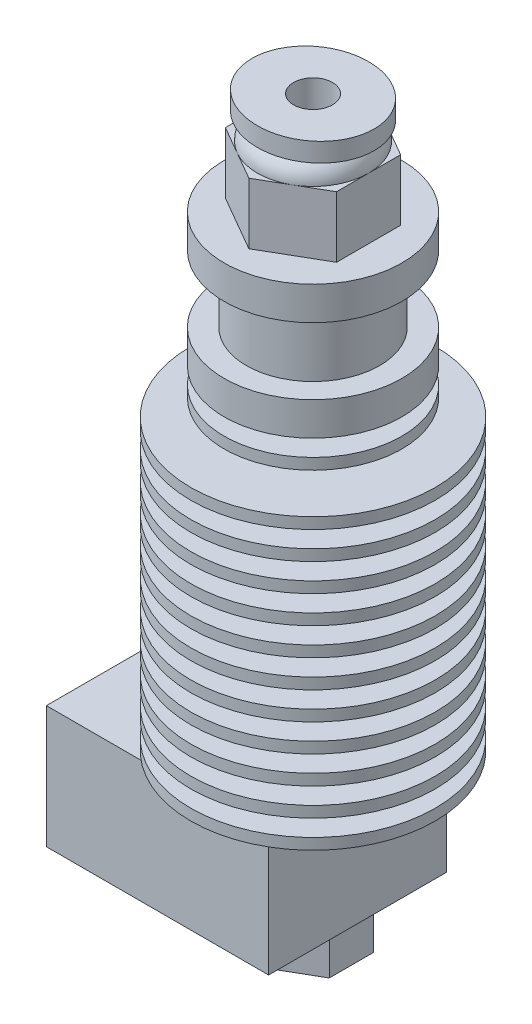
SolidWorks part; units mm, degrees
material "1023 Chapa de acero al carbono (SS)"
ref_plane "Alzado" through (0, 0, 0) normal (0, 0, 1) x (1, 0, 0)
ref_plane "Planta" through (0, 0, 0) normal (0, 1, 0) x (1, 0, 0)
ref_plane "Vista lateral" through (0, 0, 0) normal (1, 0, 0) x (0, 0, -1)
sketch "Croquis1" plane through (0, 0, 0) normal (0, 0, 1) x (1, 0, 0)
  line L0 (0, 0) -> (0, 42)
  line L1 (0, 42) -> (8, 42)
  line L2 (8, 42) -> (8, 39)
  line L3 (8, 39) -> (6, 39)
  line L4 (6, 39) -> (6, 33)
  line L5 (6, 33) -> (8, 33)
  line L6 (8, 33) -> (8, 30)
  line L7 (8, 30) -> (4.5, 30)
  line L8 (4.5, 30) -> (4.5, 28.5)
  line L9 (4.5, 28.5) -> (8, 28.5)
  line L10 (8, 28.5) -> (8, 27.5)
  line L11 (8, 27.5) -> (4.5, 27.5)
  line L12 (4.5, 27.5) -> (4.5, 26)
  line L13 (4.5, 26) -> (11, 26)
  line L14 (11, 26) -> (11, 25)
  line L15 (11, 25) -> (4.5, 25)
  line L16 (4.5, 25) -> (4.5, 23.5)
  line L17 (4.5, 23.5) -> (11, 23.5)
  line L18 (11, 23.5) -> (11, 22.5)
  line L19 (11, 22.5) -> (4.5, 22.5)
  line L21 (4.5419, 21) -> (11, 21)
  line L22 (11, 21) -> (11, 20)
  line L23 (11, 20) -> (4.5698, 20)
  line L25 (4.6116, 18.5) -> (11, 18.5)
  line L26 (11, 18.5) -> (11, 17.5)
  line L27 (11, 17.5) -> (4.6395, 17.5)
  line L29 (4.6814, 16) -> (11, 16)
  line L30 (11, 16) -> (11, 15)
  line L31 (11, 15) -> (4.7093, 15)
  line L33 (4.7512, 13.5) -> (11, 13.5)
  line L34 (11, 13.5) -> (11, 12.5)
  line L35 (11, 12.5) -> (4.7791, 12.5)
  line L37 (4.8209, 11) -> (11, 11)
  line L38 (11, 11) -> (11, 10)
  line L39 (11, 10) -> (4.8488, 10)
  line L41 (4.8907, 8.5) -> (11, 8.5)
  line L42 (11, 8.5) -> (11, 7.5)
  line L43 (11, 7.5) -> (4.9186, 7.5)
  line L45 (4.9605, 6) -> (11, 6)
  line L46 (11, 6) -> (11, 5)
  line L47 (11, 5) -> (4.9884, 5)
  line L49 (5.0302, 3.5) -> (11, 3.5)
  line L50 (11, 3.5) -> (11, 2.5)
  line L51 (11, 2.5) -> (5.0581, 2.5)
  line L53 (5.1, 1) -> (11, 1)
  line L54 (11, 1) -> (11, 0)
  line L57 (4.5, 22.5) -> (4.5419, 21)
  line L58 (4.5, 22.5) -> (4.5, 21) [skipped]
  line L59 (4.5, 20) -> (4.5, 18.5) [skipped]
  line L60 (4.5, 17.5) -> (4.5, 16) [skipped]
  line L61 (4.5, 15) -> (4.5, 13.5) [skipped]
  line L62 (4.5, 12.5) -> (4.5, 11) [skipped]
  line L63 (4.5, 10) -> (4.5, 8.5) [skipped]
  line L64 (4.5, 7.5) -> (4.5, 6) [skipped]
  line L65 (4.5, 5) -> (4.5, 3.5) [skipped]
  line L66 (4.5, 2.5) -> (4.5, 1) [skipped]
  line L67 (5.0581, 2.5) -> (5.1, 1)
  line L68 (4.9884, 5) -> (5.0302, 3.5)
  line L69 (4.9186, 7.5) -> (4.9605, 6)
  line L70 (4.8488, 10) -> (4.8907, 8.5)
  line L71 (4.7791, 12.5) -> (4.8209, 11)
  line L72 (4.7093, 15) -> (4.7512, 13.5)
  line L73 (4.5698, 20) -> (4.6116, 18.5)
  line L74 (4.6395, 17.5) -> (4.6814, 16)
  line L75 (11, 0) -> (4.5, 0) [skipped]
  line L76 (0, 0) -> (0, -0.5)
  line L77 (0, -0.5) -> (2.5, -0.5)
  line L78 (2.5, -0.5) -> (2.5, 0)
  line L79 (2.5, 0) -> (11, 0)
  dimension "D1" = 42
  dimension "D2" = 8
  dimension "D3" = 6
  dimension "D4" = 3
  dimension "D5" = 6
  dimension "D6" = 3
  dimension "D7" = 8
  dimension "D8" = 1
  dimension "D9" = 4.5
  dimension "D10" = 4.5
  dimension "D11" = 1.5
  dimension "D12" = 1.5
  dimension "D13" = 8
  dimension "D14" = 1
  dimension "D15" = 11
  dimension "D16" = 4.5
  dimension "D17" = 1.5
  dimension "D18" = 11
  dimension "D19" = 1
  dimension "D21" = 5.1
  dimension "D22" = 91.599
  dimension "D23" = 2.5
  dimension "D24" = 0.5
  dimension "D20" = 10
revolve "Revolución1" add sketch "Croquis1" angle 360 about L0
sketch "Croquis2" plane through (0, 42, 0) normal (0, 1, 0) x (1, 0, 0)
  line L1 (0, 5.7735) -> (-5, 2.8868)
  line L2 (-5, 2.8868) -> (-5, -2.8868)
  line L3 (-5, -2.8868) -> (0, -5.7735)
  line L4 (0, -5.7735) -> (5, -2.8868)
  line L5 (5, -2.8868) -> (5, 2.8868)
  line L6 (5, 2.8868) -> (0, 5.7735)
  circle A0 centre (0, 0) radius 5 construction
  dimension "D1" = 10
extrude "Saliente-Extruir1" add sketch "Croquis2" along normal blind 5.5
sketch "Croquis3" plane through (0, 47.5, 0) normal (0, 1, 0) x (1, 0, 0)
  circle A0 centre (0, 0) radius 5
  dimension "D1" = 10
extrude "Saliente-Extruir2" add sketch "Croquis3" along normal blind 2
fillet "Redondeo1" radius 2 1 edges at (0, 49.5, 5)
sketch "Croquis4" plane through (0, 49.5, 0) normal (0, 1, 0) x (1, 0, 0)
  ellipse E0 centre (0, 0) end of major axis (-5.5, 0) minor radius 5
  dimension "D1" = 11
  dimension "D2" = 5
extrude "Saliente-Extruir3" add sketch "Croquis4" along normal blind 1.7
sketch "Croquis5" plane through (0, -0.5, 0) normal (0, -1, 0) x (-1, 0, 0)
  line L1 (-4, 8) -> (16, 8)
  line L2 (-4, 8) -> (-4, -8)
  line L3 (-4, -8) -> (16, -8)
  line L4 (16, 8) -> (16, -8)
  dimension "D1" = 20
  dimension "D2" = 16
  dimension "D3" = 4
  dimension "D4" = 8
extrude "Saliente-Extruir4" add sketch "Croquis5" along normal blind 11
sketch "Croquis6" plane through (0, -11.5, 0) normal (0, -1, 0) x (1, 0, 0)
  circle A0 centre (0, 0) radius 2.5 construction
  circle A1 centre (0, 0) radius 2.5
extrude "Saliente-Extruir5" add sketch "Croquis6" along normal blind 0.5
sketch "Croquis7" plane through (0, -12, 0) normal (0, -1, 0) x (1, 0, 0)
  line L1 (0, -4) -> (3.4641, -2)
  line L2 (3.4641, -2) -> (3.4641, 2)
  line L3 (3.4641, 2) -> (0, 4)
  line L4 (0, 4) -> (-3.4641, 2)
  line L5 (-3.4641, 2) -> (-3.4641, -2)
  line L6 (-3.4641, -2) -> (0, -4)
  circle A0 centre (0, 0) radius 3.4641 construction
  dimension "D1" = 8
extrude "Saliente-Extruir6" add sketch "Croquis7" along normal blind 3
sketch "Croquis8" plane through (0, -15, 0) normal (0, -1, 0) x (1, 0, 0)
  circle A0 centre (0, 0) radius 2.15
  dimension "D1" = 4.3
extrude "Saliente-Extruir7" add sketch "Croquis8" along normal blind 2 draft 44
sketch "Croquis9" plane through (0, 51.2, 0) normal (0, 1, 0) x (1, 0, 0)
  circle A0 centre (0, 0) radius 1.75
  dimension "D1" = 3.5
extrude "Cortar-Extruir1" cut sketch "Croquis9" against normal blind 60
ref_axis "Eje1" through (0, -24.4175, 0) along (0, 1, 0)
